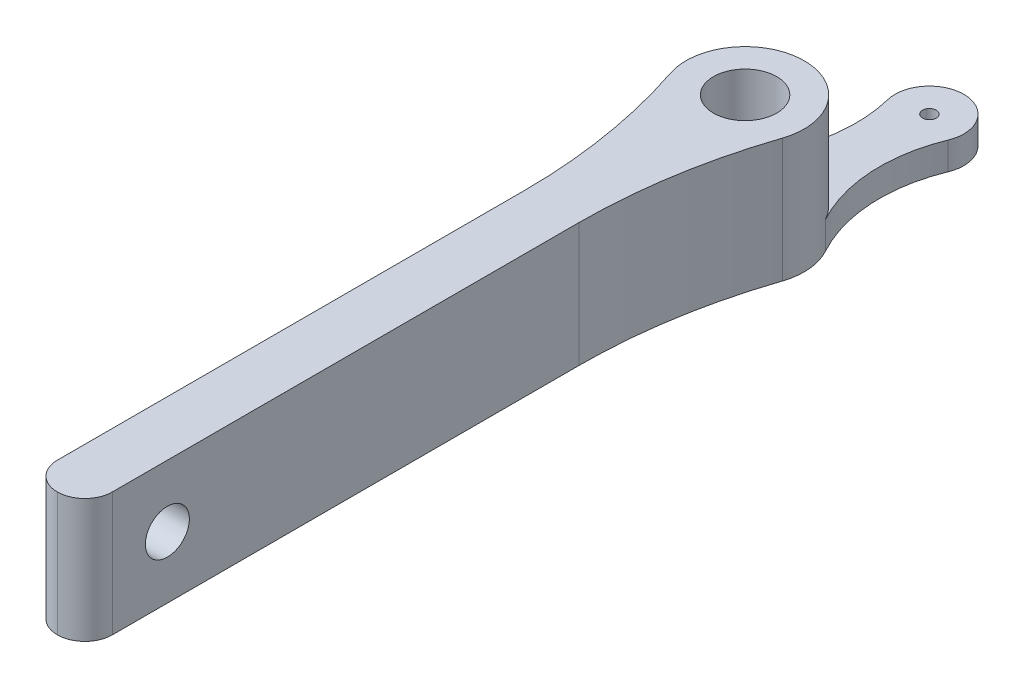
SolidWorks part; units mm, degrees
material "PE High Density"
ref_plane "Front Plane" through (0, 0, 0) normal (0, 0, 1) x (1, 0, 0)
ref_plane "Top Plane" through (0, 0, 0) normal (0, 1, 0) x (1, 0, 0)
ref_plane "Right Plane" through (0, 0, 0) normal (1, 0, 0) x (0, 0, -1)
sketch "Sketch1" plane through (0, 0, 0) normal (0, 1, 0) x (1, 0, 0)
  line L0 (0, 0) -> (0, -304.8) construction
  line L2 (-12.7, -24.1717) -> (-12.7, -304.8)
  line L3 (12.7, -24.1717) -> (12.7, -304.8)
  line L4 (-12.7, -304.8) -> (12.7, -304.8)
  line L5 (-12.7, -24.1717) -> (12.7, -24.1717) construction
  circle A0 centre (0, 0) radius 14.605
  arc A1 (12.7, -24.1717) -> (-12.7, -24.1717) centre (0, 0) ccw
  circle A2 centre (0, 0) radius 27.305 construction
  dimension "D1" = 29.21
  dimension "D3" = 304.8
  dimension "D4" = 25.4
  dimension "D2" = 12.7
extrude "Boss-Extrude1" add sketch "Sketch1" along normal blind 57.15
fillet "Fillet1" radius 254 2 edges at (-12.7, 28.575, 24.1717) (12.7, 28.575, 24.1717)
sketch "Sketch2" plane through (-12.7, 0, 0) normal (-1, 0, 0) x (0, 0, 1)
  line L0 (279.4, 57.15) -> (279.4, 0) construction
  line L1 (89.4629, 57.15) -> (304.8, 57.15) construction
  line L2 (89.4629, 0) -> (304.8, 0) construction
  line L3 (304.8, 57.15) -> (304.8, 0) construction
  circle A0 centre (279.4, 28.575) radius 10.16
  dimension "D1" = 25.4
  dimension "D2" = 20.32
extrude "Cut-Extrude1" cut sketch "Sketch2" against normal through all
sketch "Sketch6" plane through (0, 57.15, 0) normal (0, 1, 0) x (1, 0, 0)
  line L0 (0, 73.66) -> (0, 0) construction
  arc A2 (15.7418, 71.6079) -> (-15.7418, 71.6079) centre (0, 73.66) ccw
  arc A3 (15.7418, 71.6079) -> (24.83, 11.3594) centre (125.3048, 57.3252) ccw
  arc A4 (25.8874, -8.6838) -> (-25.8874, -8.6838) centre (0, 0) ccw construction
  arc A5 (-15.7418, 71.6079) -> (-24.83, 11.3594) centre (-125.3048, 57.3252) cw
  arc A6 (24.83, 11.3594) -> (-24.83, 11.3594) centre (0, 0) ccw
  circle A7 centre (0, 0) radius 14.605 construction
  circle A8 centre (0, 73.66) radius 3.175
  dimension "D1" = 73.66
  dimension "D2" = 6.35
  dimension "D3" = 110.49
  dimension "D4" = 12.7
extrude "Boss-Extrude4" [suppressed] add sketch "Sketch6" against normal offset from surface (12.7 mm away) 19.812 from offset 19.812 offset against normal yes
sketch "Sketch8" plane through (0, 0, 0) normal (0, 1, 0) x (1, 0, 0)
  line L0 (0, -304.8) -> (0, 127) construction
  line L1 (-12.7, -304.8) -> (12.7, -304.8) construction
  line L2 (0, 0) -> (5.7949, 79.2905) construction
  circle A0 centre (5.7949, 79.2905) radius 3.175
  arc A1 (20.4868, 73.2768) -> (-9.6152, 75.4768) centre (5.7949, 79.2905) ccw
  arc A2 (20.4868, 73.2768) -> (23.9257, 13.1576) centre (85.131, 46.8167) ccw
  arc A3 (25.8874, -8.6838) -> (-25.8874, -8.6838) centre (0, 0) ccw construction
  arc A4 (-9.6152, 75.4768) -> (-21.7585, 16.4964) centre (-77.4197, 58.6966) cw
  arc A5 (23.9257, 13.1576) -> (-21.7585, 16.4964) centre (0, 0) ccw
  dimension "D2" = 6.35
  dimension "D5" = 12.7
  dimension "D6" = 69.85
  dimension "D1" = 431.8
  dimension "D3" = 4.18
  dimension "D4" = 79.502
extrude "Boss-Extrude6" add sketch "Sketch8" along normal blind 12.7
sketch "Sketch9" plane through (0, 0, 304.8) normal (0, 0, 1) x (1, 0, 0)
  line L4 (-12.7, 0) -> (12.7, 0)
  line L5 (12.7, 0) -> (12.7, 57.15)
  line L6 (12.7, 57.15) -> (-12.7, 57.15)
  line L7 (-12.7, 57.15) -> (-12.7, 0)
  line L8 (-12.7, 0) -> (12.7, 0)
  line L9 (12.7, 0) -> (12.7, 57.15)
  line L10 (12.7, 57.15) -> (-12.7, 57.15)
  line L11 (-12.7, 57.15) -> (-12.7, 0)
  dimension "D1" = 0
extrude "Boss-Extrude7" add sketch "Sketch9" along normal blind 12.7
fillet "Fillet2" radius 12.7 2 edges at (-12.7, 28.575, 317.5) (12.7, 28.575, 317.5)
equation "\"A\"= 12"
equation "\"D3@Sketch1\"=\"A\""
